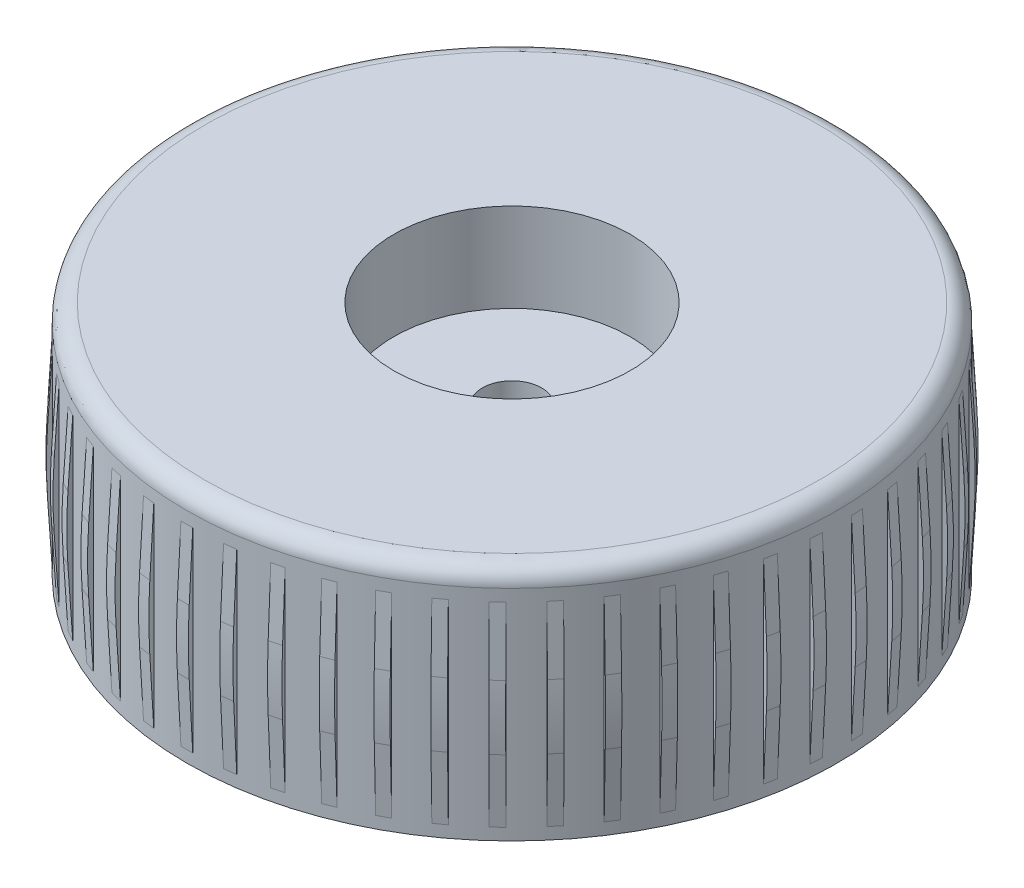
SolidWorks part; units mm, degrees
material "ABS"
ref_plane "Alzado" through (0, 0, 0) normal (0, 0, 1) x (1, 0, 0)
ref_plane "Planta" through (0, 0, 0) normal (0, 1, 0) x (1, 0, 0)
ref_plane "Vista lateral" through (0, 0, 0) normal (1, 0, 0) x (0, 0, -1)
sketch "Sketch1" plane through (0, 0, 0) normal (0, 1, 0) x (1, 0, 0)
  circle A0 centre (0, 0) radius 2.5
  circle A1 centre (0, 0) radius 27.5
  dimension "D1" = 5
  dimension "D2" = 55
extrude "Boss-Extrude1" add sketch "Sketch1" along normal blind 20
sketch "Sketch5" plane through (0, 20, 0) normal (0, 1, 0) x (1, 0, 0)
  circle A0 centre (0, 0) radius 22.225
extrude "Cut-Extrude3" cut sketch "Sketch5" against normal through all from offset 15 offset against normal yes
fillet "Fillet1" radius 1.5 1 edges at (0, 20, 27.5)
sketch "Sketch2" plane through (0, 0, 0) normal (1, 0, 0) x (0, 0, -1)
  line L0 (27.5, 17.5) -> (27.95, 9.25)
  line L1 (27.5, 0) -> (27.5, 18.5) construction
  line L2 (27.95, 9.25) -> (27.5, 1)
  line L3 (27.5, 17.5) -> (27.5, 1)
  line L4 (-27.5, 0) -> (27.5, 0) construction
  line L5 (-27.5, 18.5) -> (27.5, 18.5) construction
  point P9 (27.5, 9.25)
  dimension "D1" = 1
  dimension "D2" = 1
  dimension "D3" = 0.45
extrude "Boss-Extrude2" add sketch "Sketch2" along normal blind 0.5 and the other way blind 0.5 separate body
fillet "Fillet2" radius 50 1 edges at (0, 9.25, -27.95) type face fillet first side face at (0, 13.375, -27.725) second side face at (0, 5.125, -27.725)
pattern_circular "CirPattern3" count 50 over 360 about axis through (0, 18.5, 0) along (0, -1, 0) of bodies 102
sketch "Sketch6" plane through (0, 20, 0) normal (0, 1, 0) x (1, 0, 0)
  circle A0 centre (0, 0) radius 10
  dimension "D1" = 20
extrude "Cut-Extrude4" cut sketch "Sketch6" against normal blind 7.5
